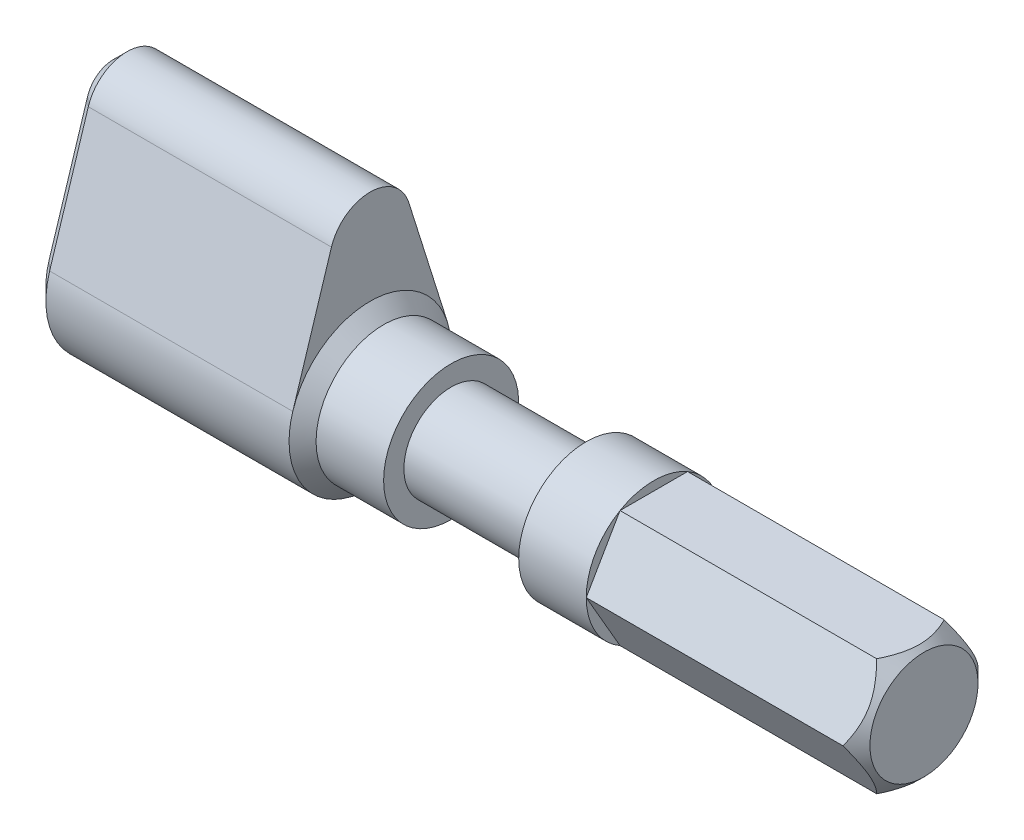
SolidWorks part; units mm, degrees
material "Cast Stainless Steel"
ref_plane "Front Plane" through (0, 0, 0) normal (0, 0, 1) x (1, 0, 0)
ref_plane "Top Plane" through (0, 0, 0) normal (0, 1, 0) x (1, 0, 0)
ref_plane "Right Plane" through (0, 0, 0) normal (1, 0, 0) x (0, 0, -1)
sketch "Sketch1" plane through (0, 0, 0) normal (0, 0, 1) x (1, 0, 0)
  line L0 (0, 0) -> (17.4479, 0) construction
  line L1 (0, 0) -> (0, 6)
  line L2 (0, 6) -> (20, 6)
  line L3 (20, 6) -> (20, 5)
  line L4 (20, 5) -> (60, 5)
  line L5 (60, 5) -> (60, 0)
  line L6 (60, 0) -> (0, 0)
  dimension "D1" = 5
  dimension "D2" = 6
  dimension "D3" = 20
  dimension "D4" = 60
revolve "Revolve1" add sketch "Sketch1" angle 360 about L0
chamfer "Chamfer1" distance 1 angle 45 2 edges at (20, 0, 6) (60, 0, 5)
sketch "Sketch2" plane through (0, 0, 0) normal (-1, 0, 0) x (0, 0, 1)
  line L0 (-2.8618, 10.9) -> (-5.7236, 1.8)
  line L1 (2.8618, 10.9) -> (5.7236, 1.8)
  line L2 (0, 0) -> (5.7236, 1.8) construction
  line L3 (0, 10) -> (-2.8618, 10.9) construction
  line L4 (0, 10) -> (2.8618, 10.9) construction
  line L5 (0, 0) -> (-5.7236, 1.8) construction
  arc A0 (2.8618, 10.9) -> (-2.8618, 10.9) centre (0, 10) ccw
  circle A1 centre (0, 0) radius 6
  circle A2 centre (0, 0) radius 6 construction
  circle M6 centre (0, 0) radius 6
  dimension "D1" = 6
  dimension "D2" = 10
extrude "Boss-Extrude1" add sketch "Sketch2" along a picked direction on the side against the normal blind 19 contours L1 A0 L0 M6
chamfer "Chamfer2" distance 1 angle 45 4 edges at (0, 13, 0) (0, 6.35, -4.2927) (0, 6.35, 4.2927) (0, -6, 0)
sketch "Sketch3" plane through (60, 0, 0) normal (1, 0, 0) x (0, 0, -1)
  line L1 (5, 0) -> (2.5, 4.3301)
  line L2 (2.5, 4.3301) -> (-2.5, 4.3301)
  line L3 (-2.5, 4.3301) -> (-5, 0)
  line L4 (-5, 0) -> (-2.5, -4.3301)
  line L5 (-2.5, -4.3301) -> (2.5, -4.3301)
  line L6 (2.5, -4.3301) -> (5, 0)
  circle A0 centre (0, 0) radius 4.3301 construction
extrude "Cut-Extrude1" cut sketch "Sketch3" against normal blind 20 flip side to cut
sketch "Sketch4" plane through (0, 0, 0) normal (0, 0, 1) x (1, 0, 0)
  line L0 (20, 5) -> (20, -5) construction
  line L1 (25, 3.5) -> (35, 3.5)
  line L2 (25, 3.5) -> (25, 7.9649)
  line L3 (25, 7.9649) -> (35, 7.9649)
  line L4 (35, 3.5) -> (35, 7.9649)
  line L5 (40, 0) -> (40, 4.3301) construction
  line L6 (40, 5) -> (20, 5) construction
  line L7 (40, 0) -> (20, 0) construction
  point P6 (35, 5.7324)
  dimension "D1" = 5
  dimension "D2" = 5
  dimension "D3" = 1.5
revolve "Cut-Revolve1" cut sketch "Sketch4" angle 360 about L7
